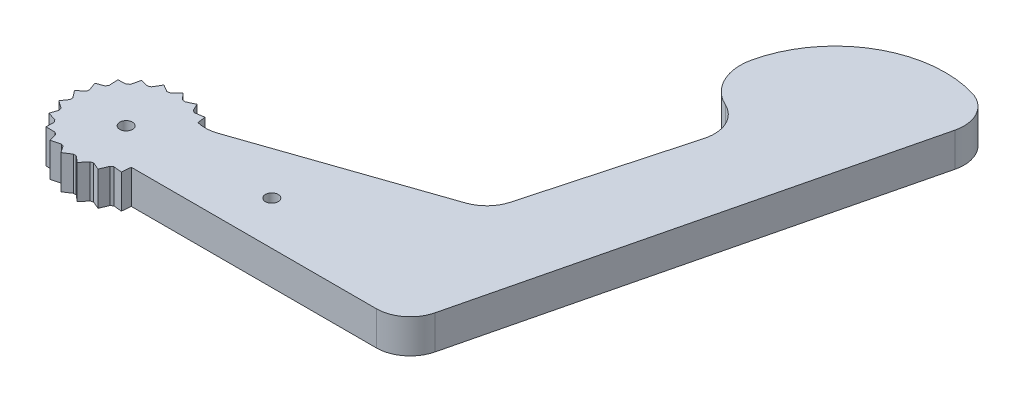
SolidWorks part; units mm, degrees
ref_plane "Front Plane" through (0, 0, 0) normal (0, 0, 1) x (1, 0, 0)
ref_plane "Top Plane" through (0, 0, 0) normal (0, 1, 0) x (1, 0, 0)
ref_plane "Right Plane" through (0, 0, 0) normal (1, 0, 0) x (0, 0, -1)
sketch "Sketch1" plane through (0, 0, 0) normal (0, 1, 0) x (1, 0, 0)
  line L0 (-29.9963, -1) -> (-29.8212, -13.6609) construction
  line L1 (-29.8212, -13.6609) -> (20.9788, -13.6609)
  line L3 (-29.9963, -1) -> (10.4102, 12.9106)
  line L4 (10.4102, 12.9106) -> (20.9788, -13.6609) construction
  line L5 (10.4102, 12.9106) -> (20.9516, 51.4212)
  line L6 (20.9516, 51.4212) -> (36.4389, 49.8724) construction
  line L7 (-37.0245, -7.4289) -> (-11.6971, -5.5098) construction
  line L8 (-29.8212, -13.6609) -> (-29.9963, -15.3628)
  line L9 (-29.9963, -15.3628) -> (-31.5245, -15.2055)
  line L11 (-31.9663, -15.4998) -> (-32.6329, -17.0755)
  line L12 (-32.6329, -17.0755) -> (-34.0478, -16.4768)
  line L14 (-34.5565, -16.6286) -> (-35.656, -17.9393)
  line L15 (-35.656, -17.9393) -> (-36.833, -16.9519)
  line L17 (-37.3638, -16.9478) -> (-38.7995, -17.8783)
  line L18 (-38.7995, -17.8783) -> (-39.6351, -16.5891)
  line L20 (-40.1413, -16.4295) -> (-41.7868, -16.8979)
  line L21 (-41.7868, -16.8979) -> (-42.2074, -15.4203)
  line L23 (-42.6445, -15.1192) -> (-44.355, -15.0843)
  line L24 (-44.355, -15.0843) -> (-44.3237, -13.5482)
  line L26 (-44.6532, -13.1322) -> (-46.2783, -12.597)
  line L27 (-46.2783, -12.597) -> (-45.7977, -11.1378)
  line L29 (-45.9907, -10.6433) -> (-47.3872, -9.655)
  line L30 (-47.3872, -9.655) -> (-46.4997, -8.4009)
  line L32 (-46.5392, -7.8716) -> (-47.5843, -6.5171)
  line L33 (-47.5843, -6.5171) -> (-46.368, -5.5786)
  line L35 (-46.2504, -5.061) -> (-46.8523, -3.4594)
  line L36 (-46.8523, -3.4594) -> (-45.4142, -2.919)
  line L38 (-45.1499, -2.4587) -> (-45.2555, -0.7511)
  line L39 (-45.2555, -0.7511) -> (-43.7221, -0.6563)
  line L41 (-43.3344, -0.2937) -> (-42.9344, 1.3697)
  line L42 (-42.9344, 1.3697) -> (-41.4406, 1.0105)
  line L44 (-40.9637, 1.2434) -> (-40.0933, 2.7163)
  line L45 (-40.0933, 2.7163) -> (-38.7706, 1.9347)
  line L47 (-38.2463, 2.0174) -> (-36.9821, 3.1702)
  line L48 (-36.9821, 3.1702) -> (-35.947, 2.035)
  line L50 (-35.4215, 1.9603) -> (-33.8747, 2.6915)
  line L51 (-33.8747, 2.6915) -> (-33.2181, 1.3025)
  line L53 (-32.7377, 1.077) -> (-31.0445, 1.3222)
  line L54 (-31.0445, 1.3222) -> (-30.8242, -0.1982)
  line L62 (-28.7046, -2.7914) -> (-27.1652, -3.5381) [skipped]
  line L63 (-27.1652, -3.5381) -> (-27.8357, -4.9204) [skipped]
  line L64 (-28.7404, -0.817) -> (-28.9758, -2.3352) [skipped]
  line L65 (-29.2398, -0.7396) -> (-28.7404, -0.817) [skipped]
  line L66 (20.9788, -13.6609) -> (42.396, 74.3527)
  arc A0 (-29.9963, -1) -> (-30.8242, -0.1982) centre (-37.0245, -7.4289) ccw
  arc A1 (42.396, 74.3527) -> (10.803, 61.671) centre (30.943, 57.1912) ccw
  arc A2 (10.803, 61.671) -> (20.9516, 51.4212) centre (19.173, 59.8093) ccw
  circle A3 centre (-37.0245, -7.4289) radius 1.1906
  circle A4 centre (-11.6971, -5.5098) radius 1.1906
  arc A5 (-31.9663, -15.4998) -> (-31.5245, -15.2055) centre (-37.0245, -7.4289) ccw
  arc A6 (-34.5565, -16.6286) -> (-34.0478, -16.4768) centre (-37.0245, -7.4289) ccw
  arc A7 (-32.7377, 1.077) -> (-33.2181, 1.3025) centre (-37.0245, -7.4289) ccw
  arc A8 (-35.4215, 1.9603) -> (-35.947, 2.035) centre (-37.0245, -7.4289) ccw
  arc A9 (-38.2463, 2.0174) -> (-38.7706, 1.9347) centre (-37.0245, -7.4289) ccw
  arc A10 (-40.9637, 1.2434) -> (-41.4406, 1.0105) centre (-37.0245, -7.4289) ccw
  arc A11 (-43.3344, -0.2937) -> (-43.7221, -0.6563) centre (-37.0245, -7.4289) ccw
  arc A12 (-45.1499, -2.4587) -> (-45.4142, -2.919) centre (-37.0245, -7.4289) ccw
  arc A13 (-46.2504, -5.061) -> (-46.368, -5.5786) centre (-37.0245, -7.4289) ccw
  arc A14 (-46.5392, -7.8716) -> (-46.4997, -8.4009) centre (-37.0245, -7.4289) ccw
  arc A15 (-37.3638, -16.9478) -> (-36.833, -16.9519) centre (-37.0245, -7.4289) ccw
  arc A16 (-40.1413, -16.4295) -> (-39.6351, -16.5891) centre (-37.0245, -7.4289) ccw
  arc A17 (-42.6445, -15.1192) -> (-42.2074, -15.4203) centre (-37.0245, -7.4289) ccw
  arc A18 (-44.6532, -13.1322) -> (-44.3237, -13.5482) centre (-37.0245, -7.4289) ccw
  arc A19 (-45.9907, -10.6433) -> (-45.7977, -11.1378) centre (-37.0245, -7.4289) ccw
  point P68 (-37.0245, -7.4289)
  dimension "D1" = 18
extrude "Boss-Extrude1" add sketch "Sketch1" along normal blind 6.35
fillet "Fillet1" radius 6.35 5 edges at (-29.9963, 3.175, 1) (10.4102, 3.175, -12.9106) (20.9516, 3.175, -51.4212) (20.9788, 3.175, 13.6609) (42.396, 3.175, -74.3527)
